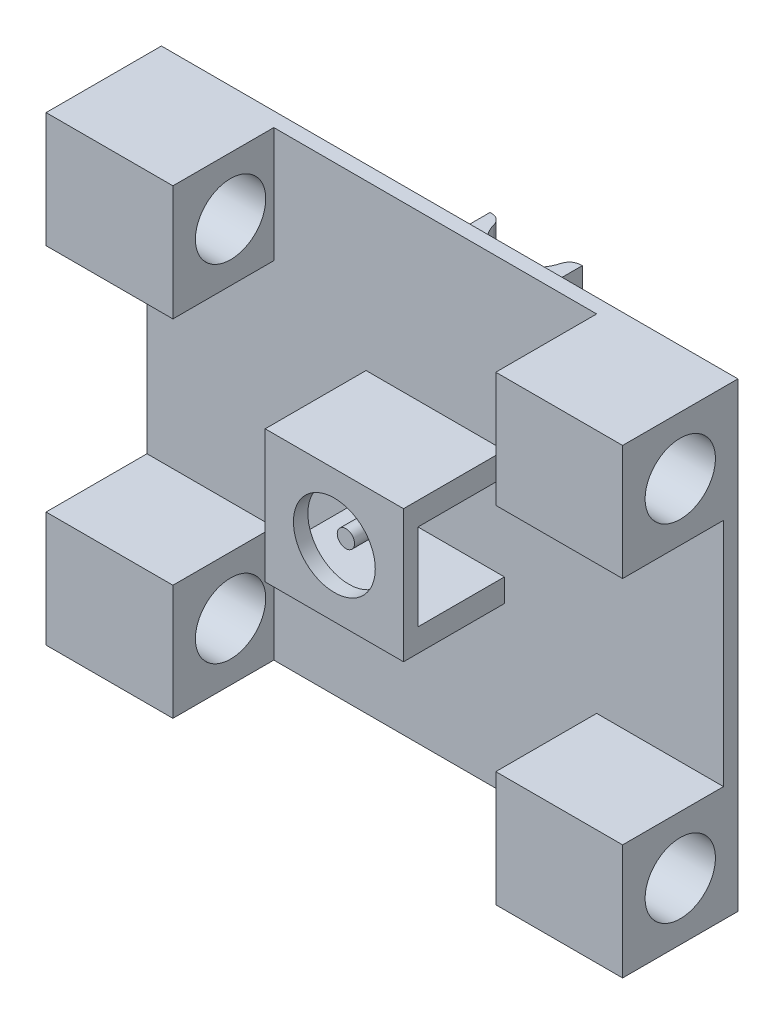
SolidWorks part; units mm, degrees
ref_plane "Front" through (0, 0, 0) normal (0, 0, 1) x (1, 0, 0)
ref_plane "Top" through (0, 0, 0) normal (0, 1, 0) x (1, 0, 0)
ref_plane "Right" through (0, 0, 0) normal (1, 0, 0) x (0, 0, -1)
sketch "Sketch1" plane through (0, 0, 0) normal (0, 0, 1) x (1, 0, 0)
  line L1 (-50, 40) -> (50, 40)
  line L2 (-50, 40) -> (-50, -40)
  line L3 (-50, -40) -> (50, -40)
  line L4 (50, 40) -> (50, -40)
  line L5 (-50, 40) -> (50, -40) construction
  line L6 (-50, -40) -> (50, 40) construction
  point P0 (0, 0)
  dimension "D1" = 80
  dimension "D2" = 100
extrude "Boss-Extrude1" add sketch "Sketch1" along normal blind 10 and the other way blind 10
sketch "Sketch2" plane through (0, 0, 0) normal (1, 0, 0) x (0, 0, -1)
  circle A0 centre (0, 30) radius 6.1
  dimension "D2" = 12.2
  dimension "D1" = 30
extrude "Cut-Extrude1" cut sketch "Sketch2" along normal through all both and the other way through all
mirror "Mirror1" about plane through (0, 0, 0) normal (0, 1, 0) of "Cut-Extrude1"
sketch "Sketch3" plane through (50, 0, 0) normal (1, 0, 0) x (0, 0, -1)
  line L1 (-7.5, 7.5) -> (7.5, 7.5)
  line L2 (-7.5, 7.5) -> (-7.5, -7.5)
  line L3 (-7.5, -7.5) -> (7.5, -7.5)
  line L4 (7.5, 7.5) -> (7.5, -7.5)
  line L5 (-7.5, 7.5) -> (7.5, -7.5) construction
  line L6 (-7.5, -7.5) -> (7.5, 7.5) construction
  point P0 (0, 0)
  dimension "D1" = 15
  dimension "D2" = 15
extrude "Cut-Extrude2" cut sketch "Sketch3" against normal blind 241
sketch "Sketch4" plane through (0, 0, 10) normal (0, 0, 1) x (1, 0, 0)
  circle A0 centre (0, 0) radius 7.1
extrude "Cut-Extrude3" cut sketch "Sketch4" against normal blind 5
sketch "Sketch5" plane through (0, 0, -7.5) normal (0, 0, 1) x (1, 0, 0)
  circle A0 centre (0, 0) radius 1.5
extrude "Boss-Extrude2" add sketch "Sketch5" along normal blind 15.5
sketch "Sketch6" plane through (0, 0, 0) normal (1, 0, 0) x (0, 0, -1)
  line L0 (7.5, 7.5) -> (-7.5, 7.5) construction
  line L1 (-13.8927, 20) -> (7.5, 20)
  line L2 (-13.8927, 20) -> (-13.8927, 11.5)
  line L3 (-13.8927, 11.5) -> (7.5, 11.5)
  line L4 (7.5, 20) -> (7.5, 11.5)
  line L8 (10, -40) -> (10, 40) construction
  circle A1 centre (0, 30) radius 6.1 construction
  dimension "D1" = 4
  dimension "D2" = 10
  dimension "D3" = 2.5
extrude "Cut-Extrude4" cut sketch "Sketch6" against normal through all both and the other way through all
mirror "Mirror2" about plane through (0, 0, 0) normal (0, 1, 0) of "Cut-Extrude4"
sketch "Sketch7" plane through (0, 0, -10) normal (0, 0, -1) x (-1, 0, 0)
  line L1 (15, 10) -> (20, 10)
  line L2 (15, 10) -> (15, -10)
  line L3 (15, -10) -> (20, -10)
  line L4 (20, 10) -> (20, -10)
  dimension "D1" = 20
  dimension "D2" = 5
  dimension "D3" = 20
  dimension "D4" = 10
extrude "Boss-Extrude3" add sketch "Sketch7" along normal blind 25
sketch "Sketch8" plane through (0, 0, 0) normal (1, 0, 0) x (0, 0, -1)
  line L0 (35, 10) -> (10, 10) construction
  line L1 (30, 10) -> (35, 10)
  line L2 (30, 10) -> (30, -10)
  line L3 (30, -10) -> (35, -10)
  line L4 (35, 10) -> (35, -10)
  dimension "D1" = 5
extrude "Boss-Extrude4" add sketch "Sketch8" along normal blind 5 and the other way up to surface (15 mm away) other way up to face at (-15, 0, -22.5)
fillet "Fillet4" radius 10 2 edges at (5, 10, -32.5) (5, -10, -32.5)
fillet "Fillet5" radius 5 2 edges at (-15, 0, -30) (-20, 0, -35)
sketch "Sketch10" plane through (0, 0, -10) normal (0, 0, -1) x (-1, 0, 0)
  line L0 (0, 40) -> (0, -40)
  line L1 (-50, 40) -> (50, 40) construction
  line L2 (50, -40) -> (-50, -40) construction
sketch "Sketch11" plane through (0, 0, -35) normal (0, 0, -1) x (-1, 0, 0)
  line L0 (-5.113, 0) -> (15, 0)
  line L1 (50, 0) -> (-50, 0) construction
  line L2 (15, -10) -> (15, 10) construction
  circle A0 centre (0, 0) radius 2.5
  dimension "D1" = 5
ref_plane "Plane12" through (0, 8.75, -32.6554) normal (0, 0.2588, -0.9659) x (-1, 0, 0)
extrude "Cut-Extrude5" cut sketch "Sketch11" against normal blind 10 contours L0 A0 | L0 A0 region at (0, 1.061, -35) region at (0, -1.061, -35)
thread "Thread1" pitch 0.25 method cut profile "Thread Profile2" start angle 0, offset 0, length 0, pitch 0.25, diameter 5
ref_plane "Plane14" through (2.5, 0, -35) normal (0, -1, 0) x (1, 0, 0)
sketch "Thread Profile2" plane through (2.5, 0, -35) normal (0, -1, 0) x (1, 0, 0)
  line L0 (0, 0) -> (0, 0.25) construction
  line L1 (0, 0) -> (0.1353, 0.0781)
  line L2 (0.1353, 0.0781) -> (0.1353, 0.1094)
  line L3 (0.1353, 0.1094) -> (0, 0.1875)
  line L4 (0.1353, 0.0937) -> (0, 0.0937) construction
  line L11 (0, 0) -> (0, 0.1875)
  point P2 (0, 0)
  dimension "Pitch" = 0.25
  dimension "Profile_Angle" = 60
  dimension "Profile_Land" = 0.0312
  dimension "Profile_Height" = 0.1353
sketch "Sketch19" plane through (0, 0, -10) normal (0, 0, -1) x (-1, 0, 0)
  line L1 (-8, 28.5) -> (8, 28.5)
  line L2 (-8, 28.5) -> (-8, 21.5)
  line L3 (-8, 21.5) -> (8, 21.5)
  line L4 (8, 28.5) -> (8, 21.5)
  line L5 (-8, 28.5) -> (8, 21.5) construction
  line L6 (-8, 21.5) -> (8, 28.5) construction
  line L7 (-8, -21.5) -> (8, -21.5)
  line L8 (-8, -21.5) -> (-8, -28.5)
  line L9 (-8, -28.5) -> (8, -28.5)
  line L10 (8, -21.5) -> (8, -28.5)
  line L11 (-8, -21.5) -> (8, -28.5) construction
  line L12 (-8, -28.5) -> (8, -21.5) construction
  point P0 (0, 25)
  point P5 (0, -25)
  dimension "D1" = 25
  dimension "D2" = 25
  dimension "D3" = 16
  dimension "D4" = 16
  dimension "D5" = 7
  dimension "D6" = 7
extrude "Boss-Extrude5" add sketch "Sketch19" along normal blind 15
sketch "Sketch20" plane through (0, -28.5, 0) normal (0, -1, 0) x (1, 0, 0)
  line L0 (8, -25) -> (-8, -25) construction
  line L1 (6, -25) -> (-6, -25)
  circle A0 centre (0, -25) radius 6
  line M4 (-8, -25) -> (8, -25)
extrude "Cut-Extrude6" cut sketch "Sketch20" against normal blind 90 contours A0 M4 region at (0, -28.5, -22.4535)
fillet "Fillet6" radius 2 4 edges at (6, -25, -25) (-6, -25, -25) (-6, 25, -25) (6, 25, -25)
sketch "Sketch21" plane through (0, 0, 10) normal (0, 0, 1) x (1, 0, 0)
  line L0 (50, 20) -> (-50, 20) construction
  line L1 (-28, 40) -> (28, 40)
  line L2 (-28, 40) -> (-28, 20)
  line L3 (-28, 20) -> (28, 20)
  line L4 (28, 40) -> (28, 20)
  line L5 (-28, 40) -> (28, 20) construction
  line L6 (-28, 20) -> (28, 40) construction
  line L7 (50, 40) -> (-50, 40) construction
  line L8 (50, 20) -> (50, 40) construction
  line L9 (-50, 40) -> (-50, 20) construction
  line L10 (50, -20) -> (-50, -20) construction
  line L11 (-28, -20) -> (28, -20)
  line L12 (-28, -20) -> (-28, -40)
  line L13 (-28, -40) -> (28, -40)
  line L14 (28, -20) -> (28, -40)
  line L15 (-28, -20) -> (28, -40) construction
  line L16 (-28, -40) -> (28, -20) construction
  line L17 (-50, -40) -> (50, -40) construction
  line L18 (50, -40) -> (50, -20) construction
  line L19 (-50, -20) -> (-50, -40) construction
  point P0 (0, 30)
  point P13 (0, -30)
  dimension "D1" = 0
  dimension "D2" = 0
  dimension "D3" = 22
  dimension "D4" = 22
  dimension "D5" = 0
  dimension "D6" = 0
  dimension "D7" = 22
  dimension "D8" = 22
extrude "Cut-Extrude7" cut sketch "Sketch21" against normal blind 17.5
sketch "Sketch22" plane through (0, 0, 10) normal (0, 0, 1) x (1, 0, 0)
  line L0 (-12, 11.5) -> (-12, -11.5)
  line L1 (-50, 11.5) -> (-12, 11.5)
  line L2 (-50, 11.5) -> (-50, -11.5)
  line L3 (-50, -11.5) -> (-12, -11.5)
  line L4 (50, 11.5) -> (50, -11.5)
  line L5 (-50, 11.5) -> (50, -11.5) construction
  line L6 (-50, -11.5) -> (50, 11.5) construction
  line L7 (12, 11.5) -> (12, -11.5)
  line L8 (12, 11.5) -> (50, 11.5)
  line L9 (12, -11.5) -> (50, -11.5)
  point P0 (0, 0)
  dimension "D1" = 12
  dimension "D2" = 12
extrude "Cut-Extrude8" cut sketch "Sketch22" against normal blind 17.5
